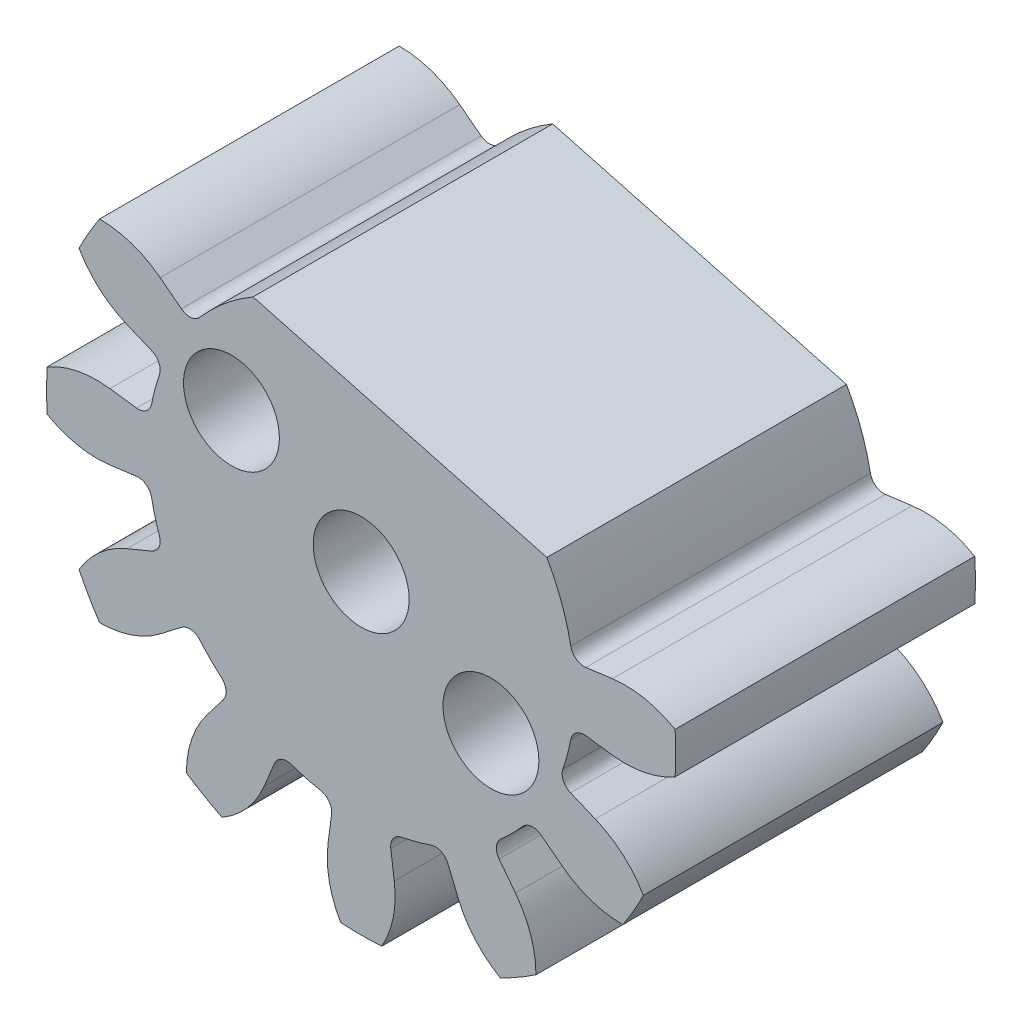
SolidWorks part; units mm, degrees
ref_plane "Front Plane" through (0, 0, 0) normal (0, 0, 1) x (1, 0, 0)
ref_plane "Top Plane" through (0, 0, 0) normal (0, 1, 0) x (1, 0, 0)
ref_plane "Right Plane" through (0, 0, 0) normal (1, 0, 0) x (0, 0, -1)
sketch "Esquisse1" plane through (0, 0, 0) normal (0, 0, 1) x (1, 0, 0)
  line L0 (0, 0) -> (22.1157, 0) construction
  line L1 (0, 0) -> (24.1492, 6.4708) construction
  line L2 (0, 0) -> (24.1492, -6.4708) construction
  line L3 (0, 0) -> (24.9429, 3.2838) construction
  line L4 (0, 0) -> (6.8822, 1.8441)
  line L5 (0, 0) -> (19.7164, -2.5957) construction
  line L6 (0, 0) -> (6.8822, -1.8441)
  line L7 (0, 0) -> (17.7915, 1.1661) construction
  line L8 (7.064, 0.93) -> (8.3849, 1.1039)
  line L9 (7.064, -0.93) -> (8.3849, -1.1039)
  line L10 (0, 0) -> (17.695, -1.1598) construction
  circle A0 centre (0, 0) radius 9 construction
  circle A1 centre (0, 0) radius 10.5 construction
  circle A2 centre (0, 0) radius 7.125 construction
  circle A3 centre (0, 0) radius 8.4572 construction
  arc A4 (6.8822, 1.8441) -> (7.064, 0.93) centre (0, 0) cw
  arc A5 (6.8822, -1.8441) -> (7.064, -0.93) centre (0, 0) ccw
  arc A6 (8.3849, 1.1039) -> (10.4775, 0.6867) centre (8.8176, -2.1828) cw
  arc A7 (10.4775, 0.6867) -> (10.4775, -0.6867) centre (0, 0) cw
  arc A8 (8.3849, -1.1039) -> (10.4775, -0.6867) centre (8.8176, 2.1828) ccw
  dimension "PrimitiveDiameter" = 18
  dimension "OutsideDiameter" = 21
  dimension "InternalDiameter" = 14.25
  dimension "BaseDiameter" = 16.9145
  dimension "DemiToothAngle" = 15
  dimension "QuartToothAngle" = 7.5
  dimension "D1" = 7.5
  dimension "D2" = 3.75
  dimension "D3" = 3.75
extrude "Boss.-Extru.2" add sketch "Esquisse1" along normal blind 10
fillet "Congé1" radius 0.45 2 edges at (7.064, -0.93, 5) (7.064, 0.93, 5)
ref_axis "Axe1" through (0, 0, 10) along (0, 0, -1)
pattern_circular "Répétition circulaire1" count 8 every 30 about axis through (0, 0, 10) along (0, 0, -1) of "Boss.-Extru.2", "Congé1"
sketch "Esquisse3" plane through (0, 0, 10) normal (0, 0, 1) x (1, 0, 0)
  circle A0 centre (0, 0) radius 1.6
  dimension "D1" = 3.2
sketch "Esquisse5" plane through (0, 0, 10) normal (0, 0, 1) x (1, 0, 0)
  circle A0 centre (0, 0) radius 7.125
  point P3 (0, 0)
extrude "Boss.-Extru.4" add sketch "Esquisse5" against normal through all
sketch "Esquisse7" plane through (0, 0, 10) normal (0, 0, 1) x (1, 0, 0)
  line L0 (-3.6089, 6.1434) -> (6.1971, 3.5159)
  line L1 (-5.385, 4.6656) -> (-3.6089, 6.1434) construction
  line L2 (6.1971, 3.5159) -> (6.9963, 1.348) construction
  circle A0 centre (0, 0) radius 7.125 construction
  arc A1 (6.1971, 3.5159) -> (-3.6089, 6.1434) centre (0, 0) ccw
  point P5 (0, 0)
  dimension "D1" = 5
extrude "Enlèv. mat.-Extru.3" cut sketch "Esquisse7" against normal through all
extrude "Enlèv. mat.-Extru.4" cut sketch "Esquisse3" against normal through all
sketch "Esquisse8" plane through (0, 0, 10) normal (0, 0, 1) x (1, 0, 0)
  line L0 (-4.3301, 2.5) -> (4.3301, -2.5) construction
  circle A0 centre (-4.3301, 2.5) radius 1.6
  circle A1 centre (4.3301, -2.5) radius 1.6
  circle A2 centre (0, 0) radius 1.6 construction
  arc A3 (-8.7304, 5.8335) -> (-9.4172, 4.644) centre (0, 0) ccw construction
  point P6 (0, 0)
  point P11 (-9.0933, 5.25)
  dimension "D1" = 5
extrude "Enlèv. mat.-Extru.5" cut sketch "Esquisse8" against normal through all
equation "\"Modulo\"= 1.5mm"
equation "\"ToothCount\"= 12"
equation "\"PrimitiveDiameter@Esquisse1\"= \"Modulo\" * \"ToothCount\""
equation "\"OutsideDiameter@Esquisse1\" = \"Modulo\" *  ( \"ToothCount\" + 2 ) "
equation "\"InternalDiameter@Esquisse1\" = \"PrimitiveDiameter@Esquisse1\" - \"Modulo\" * 2.5"
equation "\"Angle\"= 20deg"
equation "\"BaseDiameter@Esquisse1\" = \"PrimitiveDiameter@Esquisse1\" * cos ( \"Angle\" ) "
equation "\"DemiToothAngle@Esquisse1\" = 180 / \"ToothCount\""
equation "\"QuartToothAngle@Esquisse1\"= \"DemiToothAngle@Esquisse1\" / 2"
equation "\"D1@Esquisse1\"= \"QuartToothAngle@Esquisse1\""
equation "\"D2@Esquisse1\"= \"QuartToothAngle@Esquisse1\" / 2"
equation "\"D3@Esquisse1\"= \"D2@Esquisse1\""
equation "\"D2@Répétition circulaire1\"=360/\"ToothCount\""
equation "\"D1@Congé1\"=\"Modulo\"*0.3"
